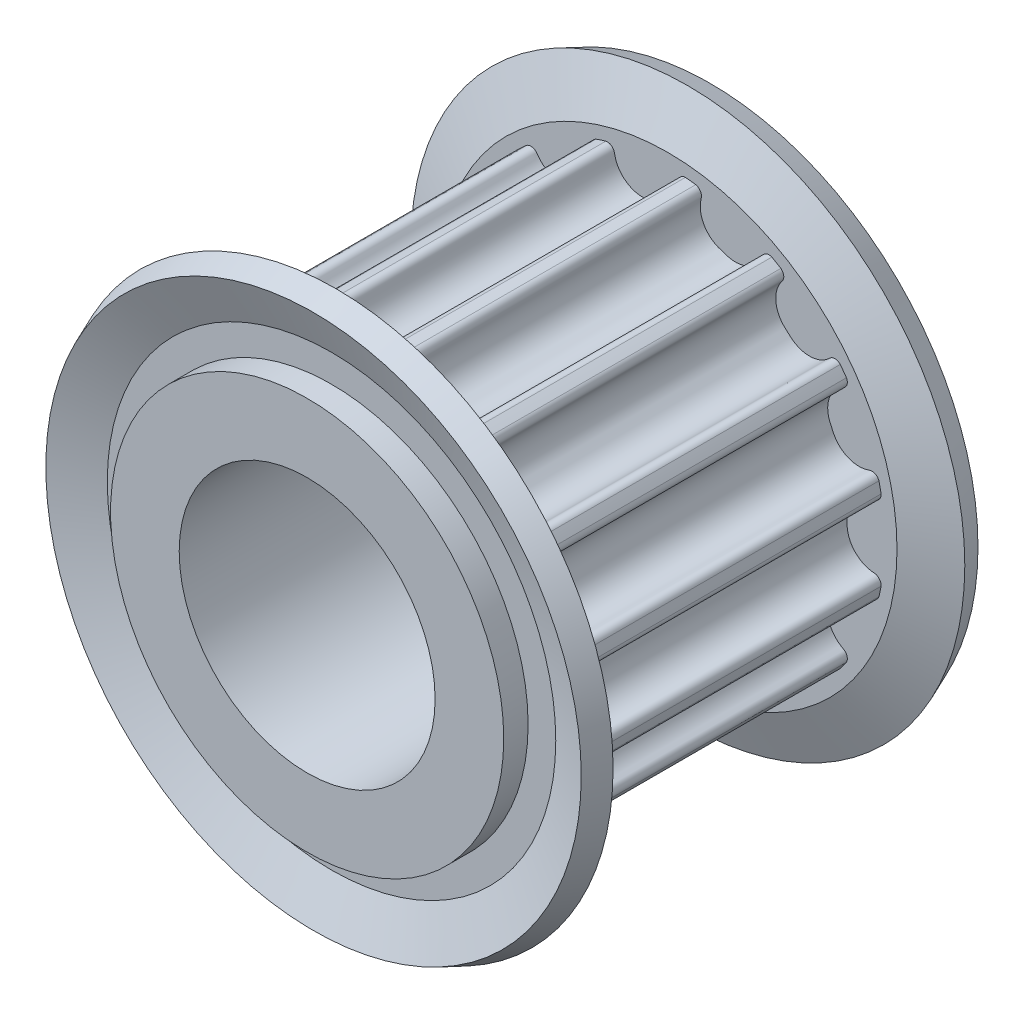
SolidWorks part; units mm, degrees
ref_plane "前视基准面" through (0, 0, 0) normal (0, 0, 1) x (1, 0, 0)
ref_plane "上视基准面" through (0, 0, 0) normal (0, 1, 0) x (1, 0, 0)
ref_plane "右视基准面" through (0, 0, 0) normal (1, 0, 0) x (0, 0, -1)
ref_axis "基准轴1" through (0, 0, 55) along (0, 0, -1)
sketch "SketchRevolveGearBelt01Pulley" plane through (0, 0, 0) normal (1, 0, 0) x (0, 0, -1)
  line L0 (0, 0) -> (1, 0) construction
  line L1 (6.4008, 0) -> (6.4008, 6.1455)
  line L2 (6.4008, 6.1455) -> (5.6388, 6.1455)
  line L3 (5.6388, 6.1455) -> (5.6388, 7.0099)
  line L4 (5.6388, 7.0099) -> (6.2015, 8.3685)
  line L5 (6.2015, 8.3685) -> (5.4975, 8.6601)
  line L6 (5.4975, 8.6601) -> (4.8768, 7.1615)
  line L7 (4.8768, 7.1615) -> (4.8768, 6.7805)
  line L8 (4.8768, 6.7805) -> (-4.8768, 6.7805)
  line L9 (-4.8768, 6.7805) -> (-4.8768, 7.1615)
  line L10 (-4.8768, 7.1615) -> (-5.4975, 8.6601)
  line L11 (-5.4975, 8.6601) -> (-6.2015, 8.3685)
  line L12 (-6.2015, 8.3685) -> (-5.6388, 7.0099)
  line L13 (-5.6388, 7.0099) -> (-5.6388, 6.1455)
  line L14 (-5.6388, 6.1455) -> (-6.4008, 6.1455)
  line L15 (-6.4008, 6.1455) -> (-6.4008, 0)
  line L16 (-6.4008, 0) -> (6.4008, 0)
  dimension "GearBeltFlange1OutsideLength" = 0.8644
  dimension "GearBeltFlange1X" = 0.5627
  dimension "GearBeltFlange1Y" = 1.3586
  dimension "GearBeltFlangeThickness" = 0.762
  dimension "GearBeltFlangeInside" = 0.381
  dimension "GearBeltOutsideDiameter" = 6.7805
  dimension "GearBeltFlange2X" = 0.5627
revolve "GearBelt01Pulley" add sketch "SketchRevolveGearBelt01Pulley" angle 360 about L0
sketch "SketchToothGearBelt01Pulley" plane through (0, 0, 0) normal (0, 0, 1) x (1, 0, 0)
  arc A0 (6.6611, 1.2728) -> (6.6611, -1.2728) centre (0, 0) cw
  spline S0 degree 3 poles (6.6611, -1.2728) (6.6636, -1.2597) (6.6656, -1.2396) (6.6648, -1.2127) (6.6624, -1.1927) (6.6583, -1.173) (6.6525, -1.1538) (6.645, -1.1351) (6.6358, -1.1171) (6.6252, -1.1) (6.6131, -1.084) (6.5996, -1.069) (6.5848, -1.0553) (6.569, -1.0429) (6.552, -1.032) (6.5342, -1.0226) (6.5157, -1.0148) (6.4965, -1.0087) (6.4769, -1.0041) (6.4278, -0.9983) (6.3619, -0.9935) (6.281, -0.9768) (6.2139, -0.9578) (6.1485, -0.9335) (6.0852, -0.9041) (6.0244, -0.8699) (5.9665, -0.8311) (5.9117, -0.7878) (5.8606, -0.7404) (5.8133, -0.6891) (5.7702, -0.6343) (5.7315, -0.5762) (5.6975, -0.5154) (5.6683, -0.452) (5.6442, -0.3865) (5.6253, -0.3194) (5.6117, -0.251) (5.6034, -0.1817) (5.6014, -0.1166) (5.6018, -0.056) (5.6017, 0) (5.6018, 0.056) (5.6014, 0.1166) (5.6034, 0.1817) (5.6117, 0.251) (5.6253, 0.3194) (5.6442, 0.3865) (5.6683, 0.452) (5.6975, 0.5154) (5.7315, 0.5762) (5.7702, 0.6343) (5.8133, 0.6891) (5.8606, 0.7404) (5.9117, 0.7878) (5.9665, 0.8311) (6.0244, 0.8699) (6.0852, 0.9041) (6.1485, 0.9335) (6.2139, 0.9578) (6.281, 0.9768) (6.3619, 0.9935) (6.4278, 0.9983) (6.4769, 1.0041) (6.4965, 1.0087) (6.5157, 1.0148) (6.5342, 1.0226) (6.552, 1.032) (6.569, 1.0429) (6.5848, 1.0553) (6.5996, 1.069) (6.6131, 1.084) (6.6252, 1.1) (6.6358, 1.1171) (6.645, 1.1351) (6.6525, 1.1538) (6.6583, 1.173) (6.6624, 1.1927) (6.6648, 1.2127) (6.6656, 1.2396) (6.6636, 1.2597) (6.6611, 1.2728) knots 0 0 0 0 0.010832 0.016248 0.021665 0.027081 0.032497 0.037913 0.043329 0.048745 0.054162 0.059578 0.064994 0.07041 0.075826 0.081242 0.086659 0.092075 0.097491 0.102907 0.132017 0.150785 0.169553 0.18832 0.207088 0.225855 0.244623 0.263391 0.282158 0.300926 0.319694 0.338461 0.357229 0.375997 0.394764 0.413532 0.4323 0.451067 0.469835 0.484917 0.5 0.515083 0.530165 0.548933 0.5677 0.586468 0.605236 0.624003 0.642771 0.661539 0.680306 0.699074 0.717842 0.736609 0.755377 0.774145 0.792912 0.81168 0.830447 0.849215 0.867983 0.897093 0.902509 0.907925 0.913341 0.918758 0.924174 0.92959 0.935006 0.940422 0.945838 0.951255 0.956671 0.962087 0.967503 0.972919 0.978335 0.983752 0.989168 1 1 1 1
extrude "ToothExtrudeCutGearBelt01Pulley" cut sketch "SketchToothGearBelt01Pulley" against normal blind 4.8768 and the other way blind 4.8768
pattern_circular "PatternGearBelt01Pulley" count 15 every 24 about axis through (0, 0, 55) along (0, 0, -1) of "ToothExtrudeCutGearBelt01Pulley"
sketch "BoreRevolveSketch" plane through (0, 0, 0) normal (1, 0, 0) x (0, 0, -1)
  line L0 (0, 0) -> (1, 0) construction
  line L1 (-6.4008, 0) -> (6.4008, 0)
  line L2 (6.4008, 0) -> (6.4008, 4)
  line L3 (6.4008, 4) -> (-6.4008, 4)
  line L4 (-6.4008, 4) -> (-6.4008, 0)
  dimension "TaperSide1" = 4
  dimension "TaperSide2" = 4
revolve "BoreRevolveCut" cut sketch "BoreRevolveSketch" angle 360 about L0
sketch "AuxiliarySketchGearBelt01Pulley" plane through (0, 0, 0) normal (0, 0, 1) x (1, 0, 0)
  circle A0 centre (0, 0) radius 7.1615 construction
  dimension "PitchDiameter" = 14.3229
